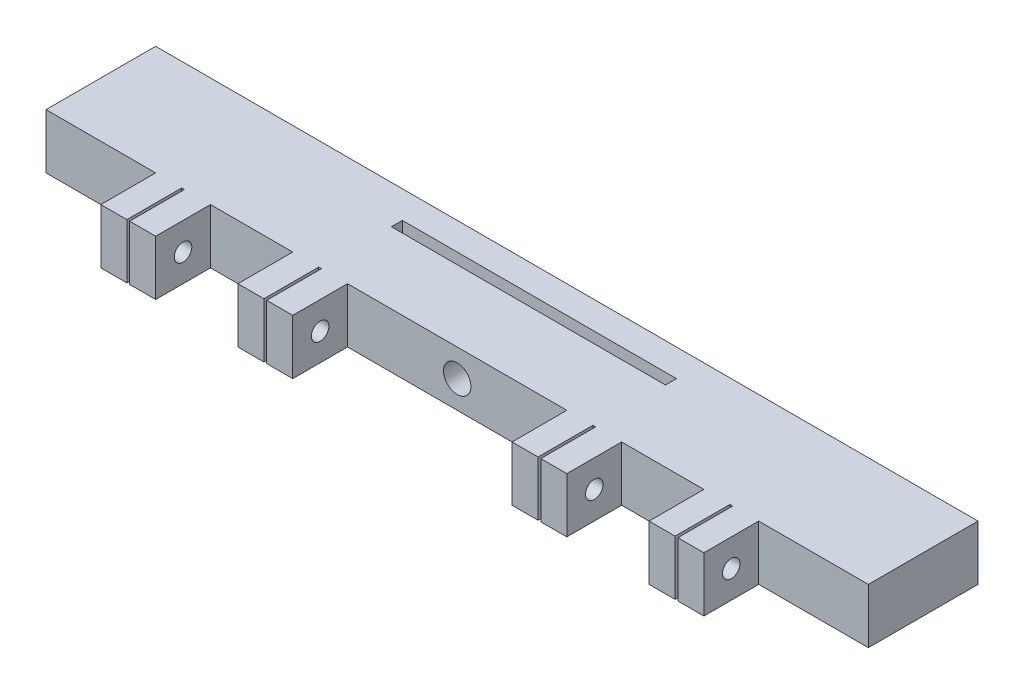
SolidWorks part; units mm, degrees
ref_plane "Front Plane" through (0, 0, 0) normal (0, 0, 1) x (1, 0, 0)
ref_plane "Top Plane" through (0, 0, 0) normal (0, 1, 0) x (1, 0, 0)
ref_plane "Right Plane" through (0, 0, 0) normal (1, 0, 0) x (0, 0, -1)
sketch "Sketch1" plane through (0, 0, 0) normal (0, 1, 0) x (1, 0, 0)
  line L0 (0, 0) -> (-75, 0)
  line L2 (-55, -30) -> (-45, -30)
  line L3 (-45, -30) -> (-45, -20)
  line L4 (-45, -20) -> (-30, -20)
  line L5 (-30, -20) -> (-30, -30)
  line L6 (-30, -30) -> (-20, -30)
  line L7 (-20, -30) -> (-20, -20)
  line L10 (20, -20) -> (20, -30)
  line L11 (20, -30) -> (30, -30)
  line L12 (30, -30) -> (30, -20)
  line L13 (30, -20) -> (45, -20)
  line L14 (45, -20) -> (45, -30)
  line L15 (45, -30) -> (55, -30)
  line L17 (75, 0) -> (0, 0)
  line L18 (-20, -20) -> (20, -20)
  line L19 (-75, 0) -> (-75, -20)
  line L20 (-75, -20) -> (-55, -20)
  line L21 (-55, -20) -> (-55, -30)
  line L22 (55, -30) -> (55, -20)
  line L23 (55, -20) -> (75, -20)
  line L24 (75, -20) -> (75, 0)
  line L25 (0, 0) -> (0, -20) construction
  point P3 (-25, -30)
  point P11 (-50, -30)
  point P24 (0, -20)
  point P26 (100, -9.5277)
  dimension "D1" = 50
  dimension "D2" = 20
  dimension "D3" = 10
  dimension "D4" = 10
  dimension "D5" = 25
  dimension "D6" = 150
extrude "Boss-Extrude1" add sketch "Sketch1" along normal blind 10
sketch "Sketch2" plane through (0, 10, 0) normal (0, 1, 0) x (1, 0, 0)
  line L0 (-55, -30) -> (-45, -30) construction
  line L1 (-49.75, -30) -> (-50.25, -30)
  line L2 (-49.75, -30) -> (-49.75, -20)
  line L3 (-49.75, -20) -> (-50.25, -20)
  line L4 (-50.25, -30) -> (-50.25, -20)
  line L5 (-30, -30) -> (-20, -30) construction
  line L6 (-24.75, -30) -> (-25.25, -30)
  line L7 (-24.75, -30) -> (-24.75, -20)
  line L8 (-24.75, -20) -> (-25.25, -20)
  line L9 (-25.25, -30) -> (-25.25, -20)
  line L10 (20, -30) -> (30, -30) construction
  line L11 (24.75, -30) -> (25.25, -30)
  line L12 (24.75, -30) -> (24.75, -20)
  line L13 (24.75, -20) -> (25.25, -20)
  line L14 (25.25, -30) -> (25.25, -20)
  line L15 (45, -30) -> (55, -30) construction
  line L16 (50.25, -30) -> (49.75, -30)
  line L17 (50.25, -30) -> (50.25, -20)
  line L18 (50.25, -20) -> (49.75, -20)
  line L19 (49.75, -30) -> (49.75, -20)
  line L20 (55, -20) -> (75, -20) construction
  line L21 (30, -20) -> (45, -20) construction
  point P24 (50, -30)
  point P25 (50, -30)
  point P30 (25, -30)
  point P31 (25, -30)
  point P32 (-25, -30)
  point P33 (-25, -30)
  point P34 (-50, -30)
  point P35 (-50, -30)
  dimension "D1" = 0.5
extrude "Cut-Extrude1" cut sketch "Sketch2" against normal through all both and the other way through all
sketch "Sketch3" plane through (-55, 0, 0) normal (-1, 0, 0) x (0, 0, 1)
  line L0 (25, 10) -> (25, 5) construction
  line L1 (20, 10) -> (30, 10) construction
  line L2 (25, 5) -> (30, 5) construction
  line L3 (30, 10) -> (30, 0) construction
  circle A0 centre (25, 5) radius 1.6
  point P2 (0, 0)
  dimension "D1" = 3.2
extrude "Cut-Extrude2" cut sketch "Sketch3" against normal through all both and the other way through all
sketch "Sketch4" plane through (0, 10, 0) normal (0, 1, 0) x (1, 0, 0)
  line L0 (0, 0) -> (0, -5) construction
  line L1 (-25, -5) -> (25, -5)
  line L2 (-25, -5) -> (-25, -7)
  line L3 (-25, -7) -> (25, -7)
  line L4 (25, -5) -> (25, -7)
  line L5 (75, 0) -> (-75, 0) construction
  dimension "D1" = 2
  dimension "D2" = 5
  dimension "D3" = 50
extrude "Cut-Extrude3" cut sketch "Sketch4" against normal through all both and the other way through all
sketch "Sketch5" plane through (0, 0, 20) normal (0, 0, 1) x (1, 0, 0)
  line L0 (0, 0) -> (0, 5) construction
  circle A0 centre (0, 5) radius 2.5
  dimension "D1" = 5
  dimension "D2" = 5
extrude "Cut-Extrude4" cut sketch "Sketch5" against normal blind 8
